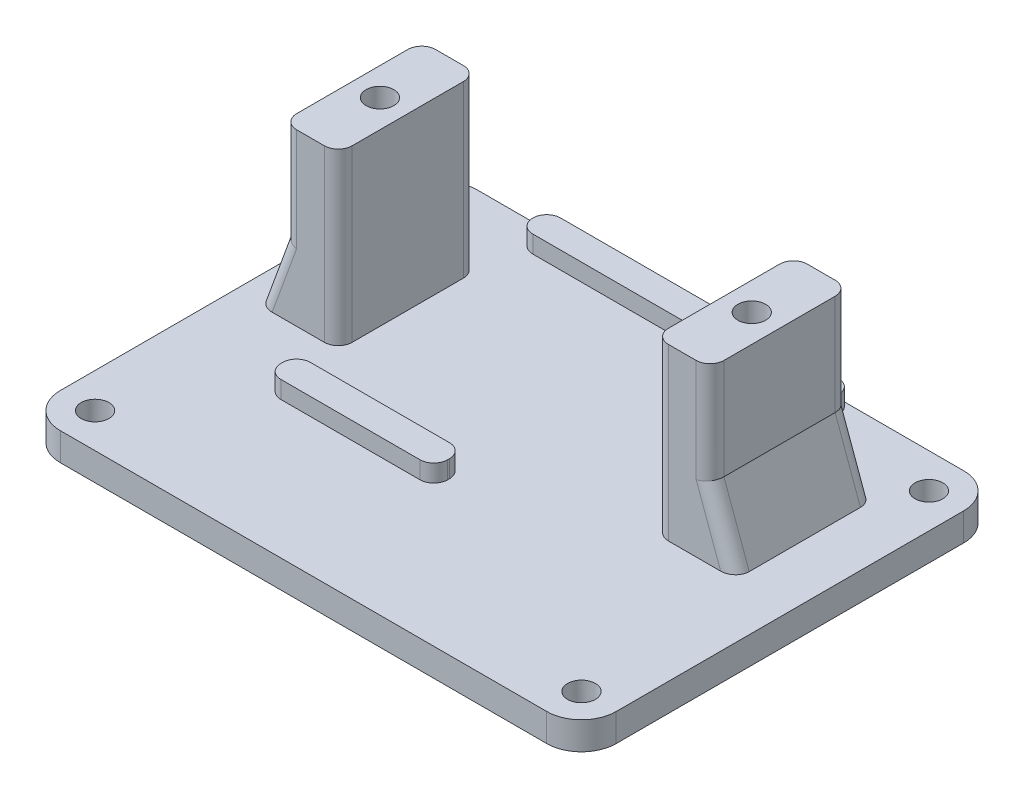
SolidWorks part; units mm, degrees
note: The reader was unsure of these and kept them because the rebuilt part matched: shared geometry of "Эскиз2<3>".
ref_plane "Спереди" through (0, 0, 0) normal (0, 0, 1) x (1, 0, 0)
ref_plane "Сверху" through (0, 0, 0) normal (0, 1, 0) x (1, 0, 0)
ref_plane "Справа" through (0, 0, 0) normal (1, 0, 0) x (0, 0, -1)
sketch "Эскиз1" plane through (0, 0, 0) normal (0, 1, 0) x (1, 0, 0)
  line L1 (-40, -30) -> (40, -30)
  line L2 (-40, -30) -> (-40, 30)
  line L3 (-40, 30) -> (40, 30)
  line L4 (40, -30) -> (40, 30)
  line L5 (0, 30) -> (0, -30) construction
  line L6 (-40, 0) -> (40, 0) construction
  line L7 (-35, -25) -> (35, -25) construction
  line L8 (-35, -25) -> (-35, 25) construction
  line L9 (-35, 25) -> (35, 25) construction
  line L10 (35, -25) -> (35, 25) construction
  line L11 (0, 25) -> (0, -25) construction
  line L12 (-35, 0) -> (35, 0) construction
  circle A0 centre (-35, 25) radius 2
  circle A1 centre (35, 25) radius 2
  circle A2 centre (-35, -25) radius 2
  circle A3 centre (35, -25) radius 2
  point P0 (0, 0)
  point P6 (-35, 24.4229)
  point P7 (0, 0)
  point P12 (35.4724, 25)
  point P14 (-35, -24.5212)
  point P16 (34.5635, -25)
  dimension "D3" = 4
  dimension "D4" = 70
  dimension "D1" = 80
  dimension "D2" = 60
  dimension "D5" = 50
extrude "Бобышка-Вытянуть1" add sketch "Эскиз1" along normal blind 4
fillet "Скругление1" radius 5 4 edges at (-40, 2, -30) (40, 2, -30) (40, 2, 30) (-40, 2, 30)
sketch "Эскиз2" plane through (0, 4, 0) normal (0, 1, 0) x (1, 0, 0)
  line L0 (-25, 26) -> (19, 26)
  line L1 (-25, -6) -> (-1, -6) construction
  line L2 (-25, -6) -> (-25, 26) construction
  line L3 (-25, 26) -> (-1, 26) construction
  line L5 (-2.25, 16.8442) -> (-2.25, -2.7738) construction
  line L6 (-25, 10) -> (20.5, 10) construction
  line L7 (19, 26) -> (19, 30)
  line L8 (19, 30) -> (-25, 30)
  line L15 (20.5, 20) -> (28.5, 20)
  line L16 (28.5, 20) -> (28.5, 0)
  line L17 (28.5, 0) -> (20.5, 0)
  line L19 (-25, 30) -> (-25, 26)
  line L24 (-33, 0) -> (-25, 0)
  line L25 (-33, 20) -> (-33, 0)
  line L26 (-25, 20) -> (-33, 20)
  line L28 (20.5, 13.3585) -> (20.5, -22.7271) construction
  line L29 (-25, -6) -> (-1, -6)
  line L30 (-40, 25) -> (-40, -25) construction
  line L39 (-25, 20) -> (-25, 0)
  line L40 (-25, -6) -> (-25, -10.25)
  line L41 (-25, -10.25) -> (-1, -10.25)
  line L42 (-1, -6) -> (-1, -10.25)
  line L43 (20.5, 20) -> (20.5, 0)
  line L44 (35, 30) -> (-35, 30) construction
  point P0 (-2.25, 10)
  point P20 (0, 0)
  point P21 (0, 0)
  dimension "D1" = 24
  dimension "D2" = 32
  dimension "D3" = 4
  dimension "D4" = 44
  dimension "D5" = 20
  dimension "D6" = 8
  dimension "D7" = 6
  dimension "D8" = 7
  dimension "D9" = 6
  dimension "D10" = 20
  dimension "D11" = 4.25
  dimension "D12" = 45.5
  dimension "D13" = 8
  dimension "D14" = 6
extrude "Бобышка-Вытянуть2" add sketch "Эскиз2" along normal blind 2.5
extrude "Бобышка-Вытянуть3" add sketch "Эскиз2<3>" along normal blind 24.5
sketch "Эскиз2<3>" plane through (0, 4, 0) normal (0, 1, 0) x (1, 0, 0) same geometry as "Эскиз2"
sketch "Эскиз3" plane through (0, 28.5, 0) normal (0, 1, 0) x (1, 0, 0)
  line L0 (-29, 20) -> (-29, 10) construction
  line L1 (-25, 20) -> (-33, 20) construction
  line L2 (-29, 10) -> (24.5, 10) construction
  line L3 (24.5, 10) -> (24.5, 14.2462) construction
  line L4 (20.5, 20) -> (28.5, 20) construction
  line L7 (20.5, 20) -> (20.5, 0) construction
  circle A1 centre (-29, 10) radius 2
  circle A2 centre (24.5, 10) radius 2
  point P10 (-0.3912, -4.8174)
  point P11 (24.5, 20)
  point P14 (20.5, 10)
  dimension "D1" = 4
extrude "Вырез-Вытянуть1" cut sketch "Эскиз3" against normal blind 7
chamfer "Фаска1" distance 10 angle 20 2 edges at (28.5, 4, -10) (-33, 4, -10) first distance on face at (28.5, 16.25, -10) first distance on face at (-33, 16.25, -10)
fillet "Скругление2" radius 2 12 edges at (30.3199, 9, -20) (30.3199, 9, 0) (-34.8199, 9, -20) (-34.8199, 9, 0) (28.5, 21.25, -20) (28.5, 21.25, 0) (20.5, 16.25, -20) (20.5, 16.25, 0) (-25, 16.25, 0) (-33, 21.25, -20) (-25, 16.25, -20) (-33, 21.25, 0)
fillet "Скругление3" radius 2 8 edges at (-25, 5.25, -26) (19, 5.25, -30) (-25, 5.25, -30) (19, 5.25, -26) (-1, 5.25, 6) (-25, 5.25, 6) (-25, 5.25, 10.25) (-1, 5.25, 10.25)
